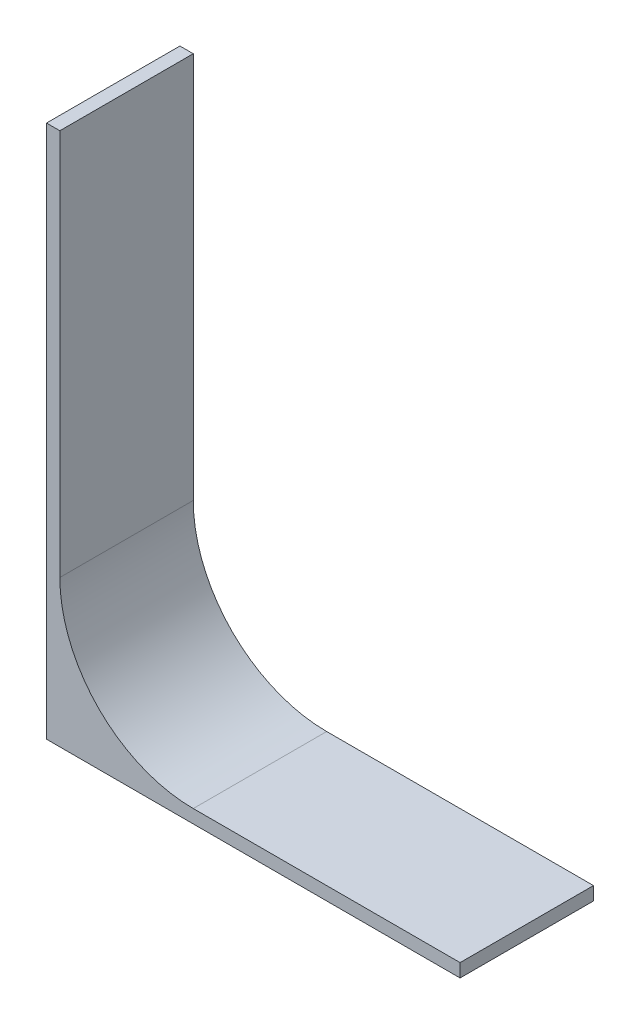
SolidWorks part; units mm, degrees
ref_plane "Front Plane" through (0, 0, 0) normal (0, 0, 1) x (1, 0, 0)
ref_plane "Top Plane" through (0, 0, 0) normal (0, 1, 0) x (1, 0, 0)
ref_plane "Right Plane" through (0, 0, 0) normal (1, 0, 0) x (0, 0, -1)
ref_axis "Axis1" through (0, -55, 0) along (0, 1, 0)
sketch "Sketch1" plane through (0, 0, 0) normal (0, 1, 0) x (1, 0, 0)
  line L1 (0, 0) -> (30, 0)
  line L2 (0, 0) -> (0, 10)
  line L3 (0, 10) -> (30, 10)
  line L4 (30, 0) -> (30, 10)
extrude "Boss-Extrude1" add sketch "Sketch1" along normal blind 1
sketch "Sketch4" plane through (0, 0, 0) normal (1, 0, 0) x (0, 0, -1)
  line L1 (0, 0) -> (10, 0)
  line L2 (0, 0) -> (0, 40)
  line L3 (0, 40) -> (10, 40)
  line L4 (10, 0) -> (10, 40)
extrude "Boss-Extrude2" add sketch "Sketch4" against normal blind 1
fillet "Fillet2" radius 10 1 edges at (0, 1, -5) type face fillet first side face at (15, 1, -5) second side face at (0, 20.5, -5)
